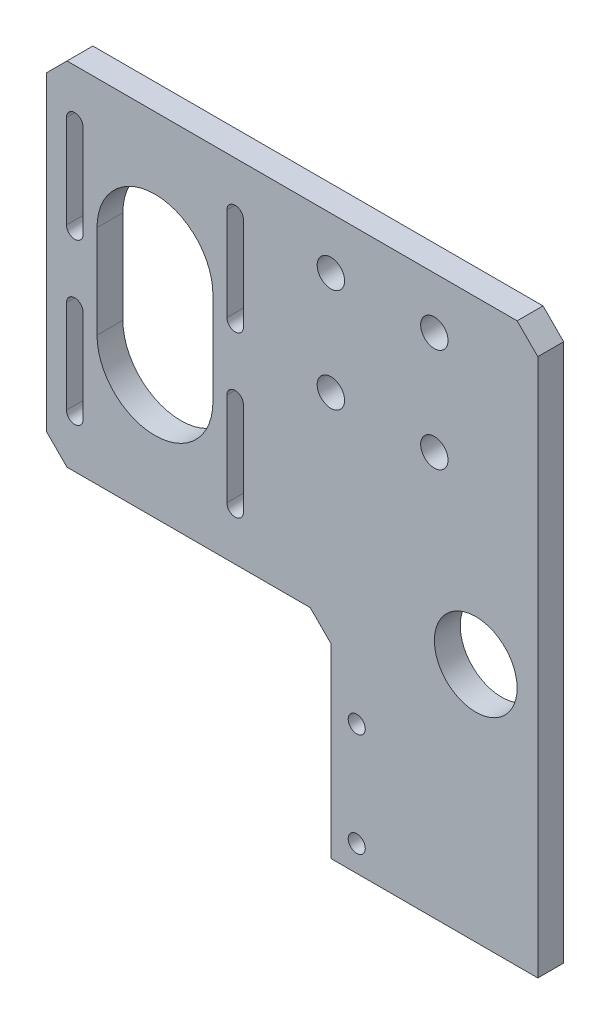
SolidWorks part; units mm, degrees
material "5052-O"
ref_plane "前基準面" through (0, 0, 0) normal (0, 0, 1) x (1, 0, 0)
ref_plane "上基準面" through (0, 0, 0) normal (0, 1, 0) x (1, 0, 0)
ref_plane "右基準面" through (0, 0, 0) normal (1, 0, 0) x (0, 0, -1)
sketch "草圖1" plane through (0, 0, 0) normal (0, 0, 1) x (1, 0, 0)
  line L1 (-47.5, -34) -> (47.5, -34)
  line L2 (-47.5, -34) -> (-47.5, 34)
  line L3 (-47.5, 34) -> (47.5, 34)
  line L4 (47.5, -34) -> (47.5, 34)
  line L5 (-47.5, -34) -> (47.5, 34) construction
  line L6 (-47.5, 34) -> (47.5, -34) construction
  point P0 (0, 0)
  dimension "D1" = 95
  dimension "D2" = 68
extrude "填料-伸長1" add sketch "草圖1" along normal blind 5
hole_wizard "M5 餘隙孔1" positions "草圖2" profile "草圖3" hole size "M5" standard "Ansi Metric" end condition through all
sketch "草圖2" plane through (0, 0, 5) normal (0, 0, 1) x (1, 0, 0)
  line L0 (47.5, 14) -> (17.5, 14) construction
  line L3 (7.5, 4) -> (27.5, 4) construction
  line L4 (7.5, 4) -> (7.5, 24) construction
  line L5 (7.5, 24) -> (27.5, 24) construction
  line L6 (27.5, 4) -> (27.5, 24) construction
  line L7 (7.5, 4) -> (27.5, 24) construction
  line L8 (7.5, 24) -> (27.5, 4) construction
  line L9 (47.5, 34) -> (-47.5, 34) construction
  line L10 (47.5, -34) -> (47.5, 34) construction
  point P6 (27.5, 24)
  point P15 (7.5, 4)
  point P16 (7.5, 24)
  point P17 (27.5, 4)
  dimension "D1" = 30
  dimension "D2" = 20
  dimension "D3" = 20
  dimension "D4" = 20
sketch "草圖3" plane through (27.5, 4, 5) normal (1, 0, 0) x (0, -1, 0)
  line L0 (0, 0) -> (0, 5)
  line L1 (0, 5) -> (2.65, 5)
  line L2 (2.65, 5) -> (2.65, 0)
  line L5 (2.65, 0) -> (0, 0)
  line L11 (0, -6.35) -> (0, 107.95) construction
  dimension "貫穿孔直徑" = 5.3
  dimension "貫穿孔深度" = 5
sketch "草圖6" plane through (0, 0, 5) normal (0, 0, 1) x (1, 0, 0)
  line L0 (47.5, 0) -> (-47.5, 0) construction
  line L1 (47.5, -34) -> (47.5, 34) construction
  line L2 (-26.5, -9) -> (-26.5, 9) construction
  line L3 (-37.7, -9) -> (-37.7, 9)
  line L4 (-15.3, -9) -> (-15.3, 9)
  line L6 (-42, 24.5) -> (-42, 6.5) construction
  line L7 (-42, -6.5) -> (-11, -6.5) construction
  line L8 (-42, -6.5) -> (-42, 24.5) construction
  line L9 (-42, 24.5) -> (-11, 24.5) construction
  line L10 (-11, -6.5) -> (-11, 24.5) construction
  line L11 (-42, -6.5) -> (-11, 24.5) construction
  line L12 (-42, 24.5) -> (-11, -6.5) construction
  line L13 (-40.4, 24.5) -> (-40.4, 6.5)
  line L14 (-43.6, 24.5) -> (-43.6, 6.5)
  line L15 (-11, 24.5) -> (-11, 6.5) construction
  line L16 (-9.4, 24.5) -> (-9.4, 6.5)
  line L17 (-12.6, 24.5) -> (-12.6, 6.5)
  line L18 (-11, -6.5) -> (-11, -24.5) construction
  line L19 (-9.4, -6.5) -> (-9.4, -24.5)
  line L20 (-12.6, -6.5) -> (-12.6, -24.5)
  line L21 (-42, -6.5) -> (-42, -24.5) construction
  line L22 (-40.4, -6.5) -> (-40.4, -24.5)
  line L23 (-43.6, -6.5) -> (-43.6, -24.5)
  line L25 (-47.5, 34) -> (-47.5, -34) construction
  arc A0 (-37.7, -9) -> (-15.3, -9) centre (-26.5, -9) ccw
  arc A1 (-15.3, 9) -> (-37.7, 9) centre (-26.5, 9) ccw
  arc A2 (-40.4, 24.5) -> (-43.6, 24.5) centre (-42, 24.5) ccw
  arc A3 (-43.6, 6.5) -> (-40.4, 6.5) centre (-42, 6.5) ccw
  arc A4 (-9.4, 24.5) -> (-12.6, 24.5) centre (-11, 24.5) ccw
  arc A5 (-12.6, 6.5) -> (-9.4, 6.5) centre (-11, 6.5) ccw
  arc A6 (-9.4, -6.5) -> (-12.6, -6.5) centre (-11, -6.5) ccw
  arc A7 (-12.6, -24.5) -> (-9.4, -24.5) centre (-11, -24.5) ccw
  arc A8 (-40.4, -6.5) -> (-43.6, -6.5) centre (-42, -6.5) ccw
  arc A9 (-43.6, -24.5) -> (-40.4, -24.5) centre (-42, -24.5) ccw
  point P6 (-26.5, 0)
  point P13 (-26.5, 9)
  point P18 (-42, 15.5)
  point P24 (-11, 15.5)
  point P30 (-11, -15.5)
  point P36 (-42, -15.5)
  dimension "D3" = 11.2
  dimension "D7" = 1.6
  dimension "D1" = 18
  dimension "D2" = 21
  dimension "D4" = 0
  dimension "D5" = 31
  dimension "D6" = 31
extrude "除料-伸長2" cut sketch "草圖6" against normal through all
sketch "草圖8" plane through (0, -34, 0) normal (0, -1, 0) x (1, 0, 0)
  line L0 (-47.5, 0) -> (47.5, 0) construction
  line L1 (47.5, 5) -> (7.5, 5)
  line L2 (47.5, 5) -> (47.5, 0)
  line L3 (47.5, 0) -> (7.5, 0)
  line L4 (7.5, 5) -> (7.5, 0)
  dimension "D1" = 40
extrude "填料-伸長2" add sketch "草圖8" along normal blind 40
sketch "草圖4" plane through (0, 0, 5) normal (0, 0, 1) x (1, 0, 0)
  line L0 (35.5, -27.5) -> (35.5, -34) construction
  line L1 (-47.5, -34) -> (7.5, -34) construction
  line L2 (47.5, -74) -> (47.5, 34) construction
  circle A0 centre (35.5, -27.5) radius 8
  dimension "D3" = 16
  dimension "D1" = 6.5
  dimension "D2" = 12
extrude "除料-伸長1" cut sketch "草圖4" against normal through all
chamfer "導角1" distance 4 angle 45 4 edges at (7.5, -34, 2.5) (-47.5, -34, 2.5) (47.5, 34, 2.5) (-47.5, 34, 2.5)
hole_wizard "M4x0.7 螺紋孔1" positions "草圖9" profile "草圖11" tap size "M4x0.7" standard "Ansi Metric" end condition through all
sketch "草圖9" plane through (0, 0, 5) normal (0, 0, 1) x (1, 0, 0)
  line L0 (12.5, -49) -> (12.5, -69) construction
  line L1 (47.5, -74) -> (47.5, 30) construction
  line L2 (47.5, -74) -> (7.5, -74) construction
  point P0 (12.5, -49)
  point P1 (12.5, -69)
  dimension "D1" = 20
  dimension "D2" = 35
  dimension "D3" = 5
sketch "草圖11" plane through (12.5, -49, 5) normal (1, 0, 0) x (0, -1, 0)
  line L0 (0, 0) -> (0, 5)
  line L1 (0, 5) -> (1.65, 5)
  line L2 (1.65, 5) -> (1.65, 0)
  line L5 (1.65, 0) -> (0, 0)
  line L11 (0, -6.35) -> (0, 107.95) construction
  dimension "貫穿螺孔鑽直徑" = 3.3
  dimension "貫穿螺孔鑽深度" = 5
